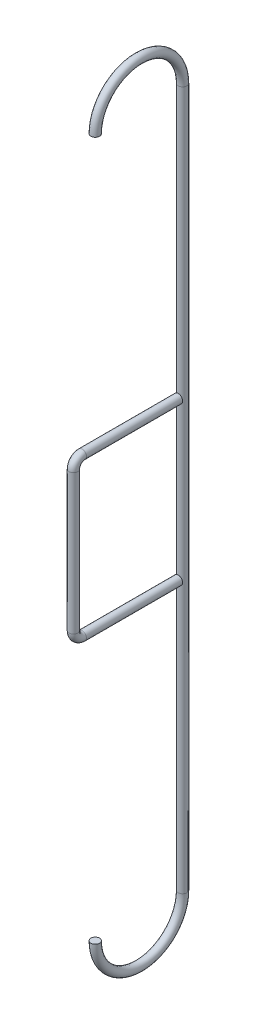
SolidWorks part; units mm, degrees
ref_plane "Front Plane" through (0, 0, 0) normal (0, 0, 1) x (1, 0, 0)
ref_plane "Top Plane" through (0, 0, 0) normal (0, 1, 0) x (1, 0, 0)
ref_plane "Right Plane" through (0, 0, 0) normal (1, 0, 0) x (0, 0, -1)
sketch "Sketch1" plane through (0, 0, 0) normal (1, 0, 0) x (0, 0, -1)
  line L0 (31.75, 254) -> (31.75, -254)
  line L1 (55, 0) -> (-55, 0) construction
  line L2 (0, 55) -> (0, -55) construction
  arc A0 (31.75, 254) -> (-31.75, 254) centre (0, 254) ccw
  arc A1 (31.75, -254) -> (-31.75, -254) centre (0, -254) cw
  point P6 (31.75, 0)
  dimension "D1" = 31.75
  dimension "D2" = 508
ref_plane "Plane1" through (0, 254, 0) normal (0, 1, 0) x (1, 0, 0)
sketch "Sketch2" plane through (0, 254, 0) normal (0, 1, 0) x (1, 0, 0)
  circle A0 centre (0, -31.75) radius 3.175
  point P2 (0, 0)
  point P6 (0, 0)
  point P8 (0, 0)
  dimension "D1" = 6.35
sweep "Sweep1" add profiles "Sketch2" path "Sketch1"
sketch "Sketch4" plane through (0, 0, 0) normal (1, 0, 0) x (0, 0, -1)
  line L0 (28.575, 57.15) -> (-41.275, 57.15)
  line L1 (28.575, 254) -> (28.575, -254) construction
  line L2 (28.575, 57.15) -> (28.575, -57.15) construction
  line L3 (28.575, -57.15) -> (-41.275, -57.15)
  line L4 (-47.625, 50.8) -> (-47.625, -50.8)
  line L5 (55, 0) -> (-55, 0) construction
  arc A0 (-47.625, 50.8) -> (-41.275, 57.15) centre (-41.275, 50.8) cw
  arc A1 (-41.275, -57.15) -> (-47.625, -50.8) centre (-41.275, -50.8) cw
  point P1 (0, 0)
  point P8 (-47.625, 0)
  point P12 (0, 0)
  point P15 (0, 0)
  point P16 (0, 0)
  point P17 (0, 0)
  dimension "D3" = 6.35
  dimension "D1" = 76.2
  dimension "D2" = 101.6
ref_plane "Plane2" through (0, 0, -28.575) normal (0, 0, 1) x (1, 0, 0)
sketch "Sketch5" plane through (0, 0, -28.575) normal (0, 0, 1) x (1, 0, 0)
  line L0 (0, 57.15) -> (0, -57.15) construction
  line L1 (0, 50.8) -> (0, 57.15) construction
  circle A0 centre (0, 57.15) radius 3.175
  point P6 (0, 0)
  dimension "D1" = 6.35
sweep "Sweep2" add profiles "Sketch5" path "Sketch4"
ref_axis "Axis1" through (-3.4925, 254, 0) along (1, 0, 0)
ref_plane "Plane3" through (0, -254, 0) normal (0, 1, 0) x (1, 0, 0)
ref_axis "Axis2" through (3.4925, -254, 0) along (-1, 0, 0)
